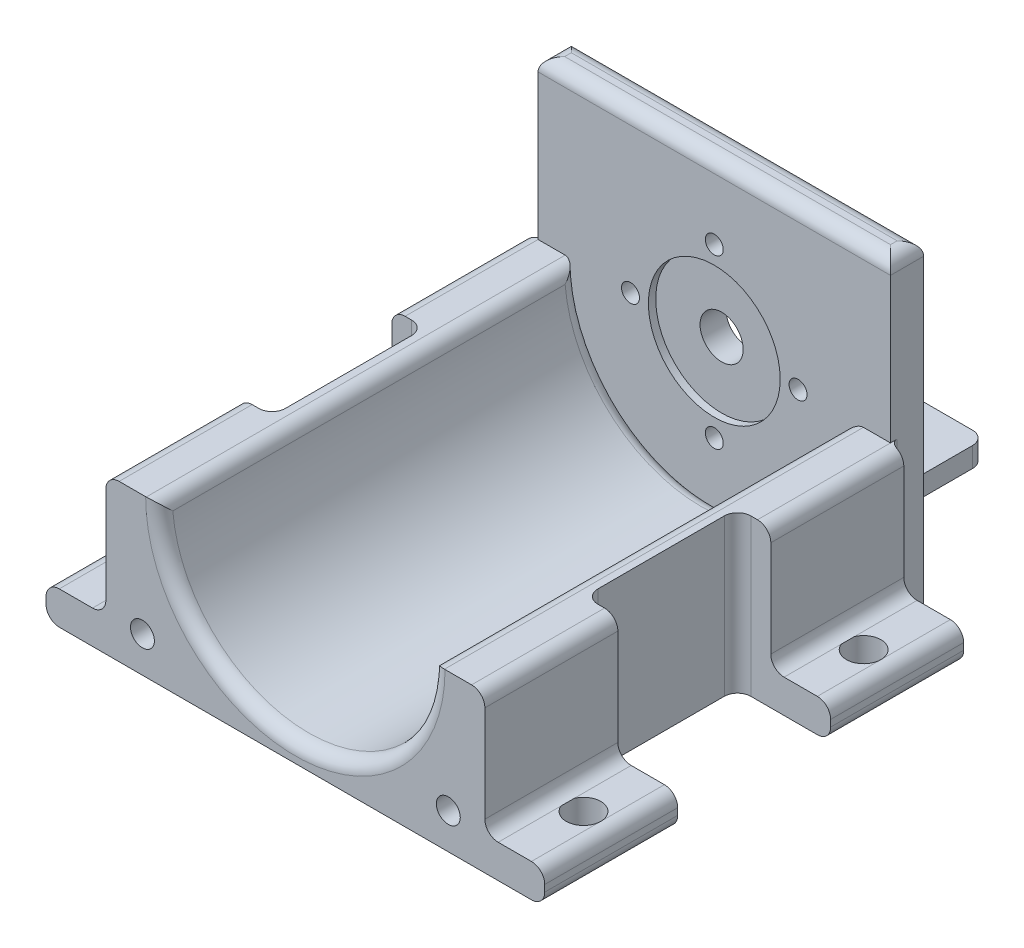
SolidWorks part; units mm, degrees
ref_plane "Front Plane" through (0, 0, 0) normal (0, 0, 1) x (1, 0, 0)
ref_plane "Top Plane" through (0, 0, 0) normal (0, 1, 0) x (1, 0, 0)
ref_plane "Right Plane" through (0, 0, 0) normal (1, 0, 0) x (0, 0, -1)
sketch "Sketch1" plane through (0, 0, 0) normal (0, 0, 1) x (1, 0, 0)
  line L0 (0, 0) -> (-29.845, 0)
  line L1 (-29.845, 0) -> (29.845, 0)
  line L2 (29.845, 0) -> (29.845, -29.845)
  line L3 (29.845, -29.845) -> (0, -29.845)
  line L4 (0, -29.845) -> (-29.845, -29.845)
  line L5 (-29.845, -29.845) -> (-29.845, 0)
  arc A0 (-26.054, 0) -> (26.054, 0) centre (0, 0) ccw
  dimension "D1" = 52.1081
extrude "Boss-Extrude1" add sketch "Sketch1" along normal blind 80.01 contours A0 L1 L5 L4 L3 L2 region at (0, -26.7214, 0)
sketch "Sketch2" plane through (0, 0, 80.01) normal (0, 0, 1) x (1, 0, 0)
  line L0 (-29.845, -23.495) -> (-29.845, 0)
  line L1 (-29.845, -29.845) -> (-45.085, -29.845)
  line L2 (-29.845, -29.845) -> (-29.845, -23.495)
  line L3 (-36.195, -23.495) -> (-45.085, -23.495)
  line L4 (-47.625, -27.305) -> (-47.625, -26.035)
  line L5 (-29.845, 0) -> (-36.195, 0)
  line L6 (-36.195, 0) -> (-36.195, -23.495)
  line L7 (0, 0) -> (0, -60.6078) construction
  line L8 (29.845, -23.495) -> (29.845, 0)
  line L9 (29.845, 0) -> (36.195, 0)
  line L10 (47.625, -27.305) -> (47.625, -26.035)
  line L11 (36.195, -23.495) -> (45.085, -23.495)
  line L12 (29.845, -29.845) -> (29.845, -23.495)
  line L13 (29.845, -29.845) -> (45.085, -29.845)
  line L14 (36.195, 0) -> (36.195, -23.495)
  arc A0 (-45.085, -29.845) -> (-47.625, -27.305) centre (-45.085, -27.305) cw
  arc A1 (-45.085, -23.495) -> (-47.625, -26.035) centre (-45.085, -26.035) ccw
  arc A2 (45.085, -29.845) -> (47.625, -27.305) centre (45.085, -27.305) ccw
  arc A3 (47.625, -26.035) -> (45.085, -23.495) centre (45.085, -26.035) ccw
  point P21 (-47.625, -29.845)
  point P24 (-47.625, -23.495)
  point P28 (47.625, -29.845)
  point P31 (47.625, -23.495)
  dimension "D3" = 2.54
  dimension "D4" = 2.54
  dimension "D1" = 17.78
  dimension "D2" = 6.35
extrude "Boss-Extrude2" add sketch "Sketch2" against normal blind 25.4
sketch "Sketch3" plane through (0, 0, 0) normal (0, 0, -1) x (-1, 0, 0)
  line L0 (-29.845, 0) -> (-36.195, 0)
  line L1 (-36.195, 0) -> (-36.195, -23.495)
  line L2 (-36.195, -23.495) -> (-45.085, -23.495)
  line L3 (-47.625, -26.035) -> (-47.625, -27.305)
  line L4 (36.195, -23.495) -> (45.085, -23.495)
  line L5 (-45.085, -29.845) -> (-29.845, -29.845)
  line L6 (-29.845, -29.845) -> (-29.845, 0)
  line L7 (0, 0) -> (0, -41.5928) construction
  line L8 (47.625, -26.035) -> (47.625, -27.305)
  line L9 (45.085, -29.845) -> (29.845, -29.845)
  line L10 (29.845, 0) -> (36.195, 0)
  line L11 (29.845, -29.845) -> (29.845, 0)
  line L12 (36.195, 0) -> (36.195, -23.495)
  arc A0 (-47.625, -27.305) -> (-45.085, -29.845) centre (-45.085, -27.305) ccw
  arc A1 (-47.625, -26.035) -> (-45.085, -23.495) centre (-45.085, -26.035) cw
  arc A2 (47.625, -26.035) -> (45.085, -23.495) centre (45.085, -26.035) ccw
  arc A3 (47.625, -27.305) -> (45.085, -29.845) centre (45.085, -27.305) cw
  dimension "D1" = 2.54
extrude "Boss-Extrude3" add sketch "Sketch3" against normal blind 25.4
fillet "Fillet1" radius 2.54 4 edges at (26.054, 0, 40.005) (0, -26.054, 80.01) (-26.054, 0, 40.005) (0, -26.054, 0)
fillet "Fillet2" radius 2.54 4 edges at (-36.195, 0, 12.7) (-36.195, 0, 67.31) (36.195, 0, 67.31) (36.195, 0, 12.7)
fillet "Fillet3" radius 2.54 4 edges at (29.845, -14.9225, 25.4) (29.845, -14.9225, 54.61) (-29.845, -14.9225, 54.61) (-29.845, -14.9225, 25.4)
fillet "Fillet4" radius 2.54 4 edges at (36.195, -23.495, 12.7) (36.195, -23.495, 67.31) (-36.195, -23.495, 67.31) (-36.195, -23.495, 12.7)
sketch "Sketch4" plane through (0, -23.495, 0) normal (0, 1, 0) x (1, 0, 0)
  line L1 (38.735, 0) -> (38.735, -25.4) construction
  line L3 (0, 0) -> (0, -97.0513) construction
  line L4 (0, -40.005) -> (67.9571, -40.005) construction
  line L5 (67.9571, -40.005) -> (-53.183, -40.005) construction
  line L6 (-45.085, -25.4) -> (-38.735, -25.4) construction
  circle A0 centre (41.783, -13.2522) radius 3.302
  circle A1 centre (-41.783, -13.2522) radius 3.302
  circle A2 centre (-41.783, -66.7578) radius 3.302
  circle A3 centre (41.783, -66.7578) radius 3.302
  dimension "D1" = 3.048
  dimension "D2" = 6.604
  dimension "D3" = 14.605
extrude "Cut-Extrude1" cut sketch "Sketch4" against normal blind 25.4
sketch "Sketch5" plane through (0, 0, 80.01) normal (0, 0, 1) x (1, 0, 0)
  line L0 (0, 0) -> (0, -55.9591) construction
  circle A0 centre (-29.21, -23.0229) radius 2.286
  arc A1 (-28.594, 0) -> (28.594, 0) centre (0, 0) ccw construction
  circle A2 centre (29.21, -23.0229) radius 2.286
  dimension "D1" = 4.572
  dimension "D2" = 29.21
extrude "Cut-Extrude2" cut sketch "Sketch5" against normal blind 19.05
sketch "Sketch6" plane through (0, 0, 0) normal (0, 0, -1) x (-1, 0, 0)
  line L0 (0, 0) -> (69.6711, 0) construction
  line L1 (-33.655, 0) -> (-33.655, -29.845)
  line L2 (69.6711, 0) -> (-17.7145, 0) construction
  line L3 (-45.085, -29.845) -> (45.085, -29.845) construction
  line L4 (-33.655, 0) -> (-33.655, 18.1047)
  line L5 (33.655, 0) -> (33.655, -29.845)
  line L6 (0, 0) -> (0, 53.7563) construction
  line L7 (33.655, -29.845) -> (-33.655, -29.845)
  line L8 (-26.054, 0) -> (-54.2672, 0) construction
  line L9 (33.655, 18.1047) -> (33.655, 0)
  line L10 (0, 53.7563) -> (0, -48.6927) construction
  line L11 (-33.655, 18.1047) -> (-33.655, 30.2589)
  line L12 (-33.655, 30.2589) -> (33.655, 30.2589)
  line L13 (33.655, 30.2589) -> (33.655, 18.1047)
  circle A1 centre (0, 0) radius 16 construction
  circle A2 centre (0, 16) radius 1.7145
  circle A3 centre (16, 0) radius 1.7145
  circle A4 centre (-16, 0) radius 1.7145
  circle A5 centre (0, -16) radius 1.7145
  dimension "D1" = 32
  dimension "D2" = 3.429
  dimension "D3" = 3.429
  dimension "D4" = 3.429
  dimension "D5" = 3.429
extrude "Boss-Extrude4" add sketch "Sketch6" along normal blind 6.35
fillet "Fillet6" radius 2.54 4 edges at (-33.655, 30.2589, -3.175) (0, 30.2589, -6.35) (33.655, 30.2589, -3.175) (0, 30.2589, 0)
fillet "Fillet8" radius 1.27 2 edges at (-33.655, -14.9225, 0) (33.655, -14.9225, 0)
sketch "Sketch8" plane through (0, -29.845, 0) normal (0, -1, 0) x (1, 0, 0)
  line L0 (-15.875, -6.35) -> (-15.875, -33.4468)
  line L2 (33.655, -6.35) -> (-33.655, -6.35) construction
  line L3 (0, 0) -> (0, -35.9868) construction
  line L4 (15.875, -6.35) -> (15.875, -33.4468)
  line L5 (-47.625, 0) -> (-47.625, -35.9868) construction
  line L6 (-13.335, -35.9868) -> (13.335, -35.9868)
  circle A0 centre (8.255, -22.9695) radius 3.302
  circle A1 centre (-8.255, -22.9695) radius 3.302
  arc A2 (-15.875, -33.4468) -> (-13.335, -35.9868) centre (-13.335, -33.4468) ccw
  arc A3 (15.875, -33.4468) -> (13.335, -35.9868) centre (13.335, -33.4468) cw
  line M17 (-33.655, -6.35) -> (33.655, -6.35)
  dimension "D2" = 6.604
  dimension "D3" = 6.604
  dimension "D4" = 7.62
  dimension "D5" = 7.62
  dimension "D6" = 2.54
  dimension "D1" = 31.75
extrude "Boss-Extrude5" add sketch "Sketch8" against normal blind 3.81 contours A3 L4 L0 A2 L6 A1 A0 M17 region at (0, -29.845, -20.9811)
fillet "Fillet9" radius 3.81 1 edges at (0, -26.035, -6.35)
fillet "Fillet10" radius 1.27 2 edges at (15.875, -26.035, -6.35) (-15.875, -26.035, -6.35)
sketch "Sketch9" plane through (0, 0, -6.35) normal (0, 0, -1) x (-1, 0, 0)
  circle A0 centre (0, 0) radius 4.1148
  dimension "D1" = 8.2296
extrude "Cut-Extrude3" cut sketch "Sketch9" against normal blind 39.116
sketch "Sketch12" plane through (0, 0, 0) normal (0, 0, 1) x (1, 0, 0)
  circle A0 centre (0, 0) radius 12.5857
  dimension "D1" = 25.1714
extrude "Cut-Extrude4" cut sketch "Sketch12" against normal blind 1.4
